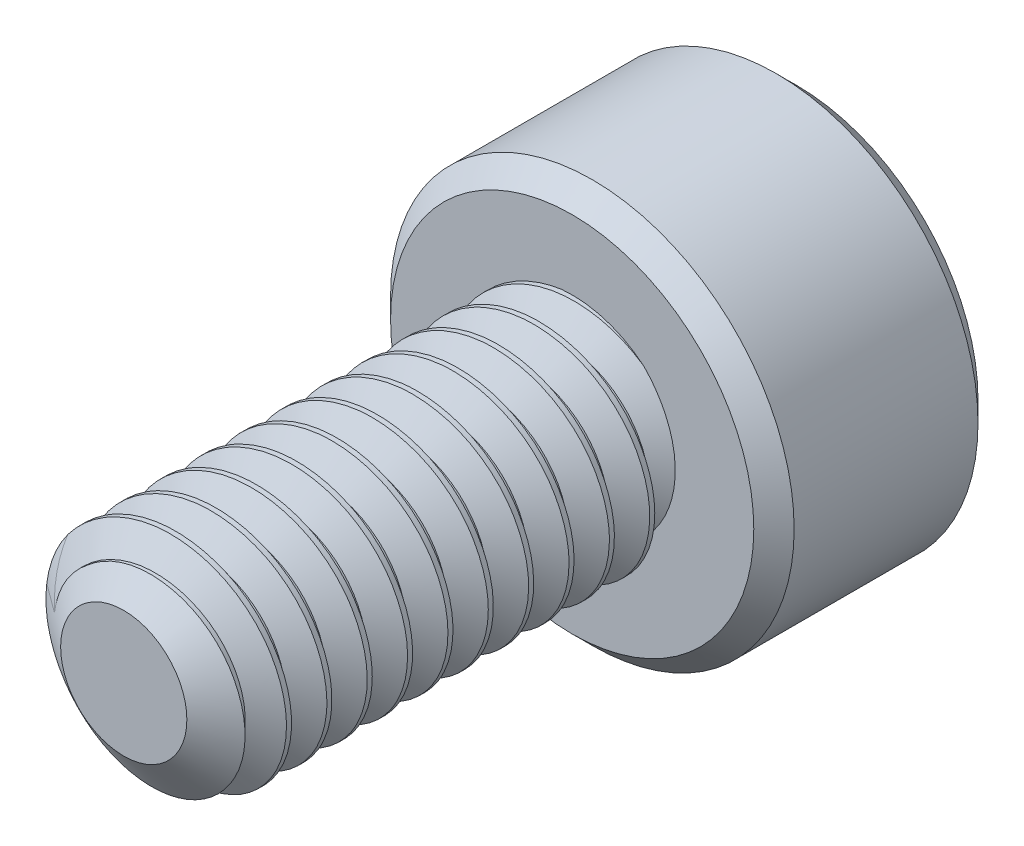
SolidWorks part; units mm, degrees
other "DetailItem1"
ref_plane "Front Plane" through (0, 0, 0) normal (0, 0, 1) x (1, 0, 0)
ref_plane "Top Plane" through (0, 0, 0) normal (0, 1, 0) x (1, 0, 0)
ref_plane "Right Plane" through (0, 0, 0) normal (1, 0, 0) x (0, 0, -1)
sketch "Sketch1" plane through (0, 0, 0) normal (0, 0, 1) x (1, 0, 0)
  circle A0 centre (0, 0) radius 1.25
  dimension "OD" = 2.5
extrude "Extrude1" add sketch "Sketch1" against normal blind 5
sketch "Sketch2" plane through (0, 0, 0) normal (0, 0, 1) x (1, 0, 0)
  circle A0 centre (0, 0) radius 1.25 construction
  circle A1 centre (0, 0) radius 1.25
curve "Helix/Spiral1" pitch 0.45 height 5.45 radius 1.25 centre (0, 0, 0) axis (0, 0, -1) start towards (0, 1, 0) parameters "pitch"=0.45
sketch "Sketch3" plane through (0, 0, 0) normal (1, 0, 0) x (0, 0, -1)
  line L0 (-0.3937, 1.25) -> (-0.225, 0.9577)
  line L1 (-0.225, 0.9577) -> (-0.1688, 0.9577)
  line L2 (-0.1688, 0.9577) -> (0, 1.25)
  line L3 (-0.3937, 1.25) -> (0, 1.25)
  line L4 (-0.1969, 1.25) -> (-0.1969, 0.9577) construction
  line L5 (-0.3094, 1.1039) -> (-0.0844, 1.1039) construction
  line L6 (0, 1.25) -> (0, -1.25) construction
  dimension "D1" = 0.0563
  dimension "D2" = 0.225
  dimension "D3" = 60
sweep "Cut-Sweep1" cut profiles "Sketch3" path "Helix/Spiral1" align with end faces yes
sketch "Sketch4" plane through (0, 0, 0) normal (1, 0, 0) x (0, 0, -1)
  line L0 (0.3825, 1.25) -> (0, 0.7037)
  line L1 (0, 0.7037) -> (0, 1.25)
  line L2 (0.3825, 1.25) -> (0, 1.25)
  line L3 (-0.3937, 1.25) -> (0, 1.25) construction
  line L4 (0, 0) -> (7.0209, 0) construction
  dimension "D1" = 55
  dimension "D2" = 0.254
revolve "Cut-Revolve1" cut sketch "Sketch4" angle 360 about L4
sketch "Sketch6" plane through (0, 0, -5) normal (0, 0, -1) x (-1, 0, 0)
  circle A0 centre (0, 0) radius 2.25
  dimension "head dia" = 4.5
extrude "Extrude2" add sketch "Sketch6" along normal blind 2.5
sketch "Sketch7" plane through (0, 0, -7.5) normal (0, 0, -1) x (-1, 0, 0)
  line L1 (0, 1.1547) -> (-1, 0.5774)
  line L2 (-1, 0.5774) -> (-1, -0.5774)
  line L3 (-1, -0.5774) -> (0, -1.1547)
  line L4 (0, -1.1547) -> (1, -0.5774)
  line L5 (1, -0.5774) -> (1, 0.5774)
  line L6 (1, 0.5774) -> (0, 1.1547)
  circle A0 centre (0, 0) radius 1 construction
  dimension "hex dia" = 2
extrude "Cut-Extrude1" cut sketch "Sketch7" against normal blind 1.5
sketch "Sketch8" plane through (0, 0, -7.5) normal (0, 0, -1) x (-1, 0, 0)
  circle A0 centre (0, 0) radius 1.1547
extrude "Cut-Extrude2" cut sketch "Sketch8" against normal through all draft 45
chamfer "Chamfer1" distance 0.225 angle 45 2 edges at (-2.25, 0, -7.5) (-2.25, 0, -5)
sketch "Sketch10" plane through (0, 0, -5) normal (0, 0, 1) x (1, 0, 0)
  circle A1 centre (0, 0) radius 1.25
  circle A2 centre (0, 0) radius 1.25
  dimension "D1" = 0
ref_plane "Plane1" through (0, 0, 0) normal (0, 0, 1) x (1, 0, 0)
extrude "partial thread" [suppressed] add sketch "Sketch10" along normal up to surface (8 mm away) separate body up to plane "Plane1"
chamfer "Chamfer2" [suppressed] distance 0.05 angle 45
combine bodies "Combine1" [suppressed] operation type add bodies to combine 107 108
sketch "Sketch9" plane through (0, 0, 0) normal (1, 0, 0) x (0, 0, -1)
  line L0 (0, 1.25) -> (0, -1.25) construction
  line L1 (1.125, 1.25) -> (1.125, -1.25) construction
  dimension "D1" = 1.125
equation "\"D3@Helix/Spiral1\" = \"screw length@Extrude1\"+\"pitch@Helix/Spiral1\""
equation "\"D1@Sketch3\" = \"pitch@Helix/Spiral1\"*.125"
equation "\"D2@Sketch3\" = \"pitch@Helix/Spiral1\"*.5"
equation "\"D1@Cut-Extrude1\" = \"hex dia@Sketch7\"*.75"
equation "\"D1@Chamfer1\" = \"head dia@Sketch6\"*.05"
equation "\"D1@Sketch9\" = \"pitch@Helix/Spiral1\"*2.5"
equation "\"D1@Chamfer2\"=\"OD@Sketch1\"*.02"
